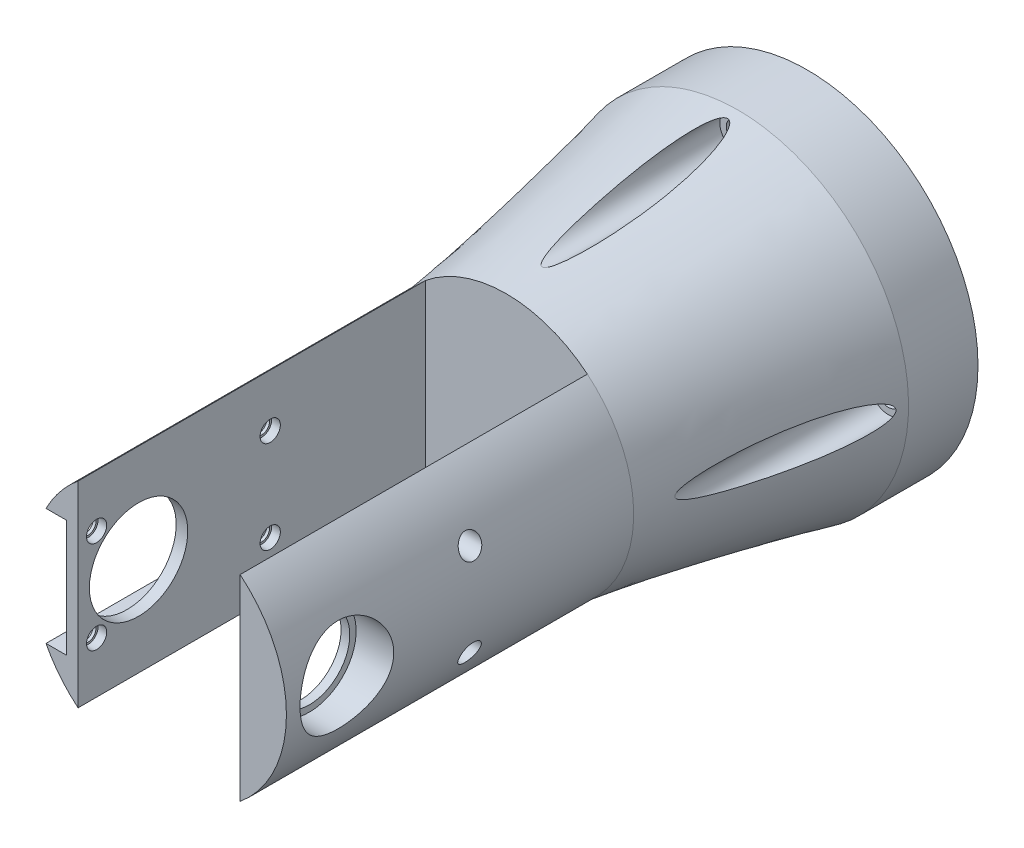
SolidWorks part; units mm, degrees
ref_plane "Front Plane" through (0, 0, 0) normal (0, 0, 1) x (1, 0, 0)
ref_plane "Top Plane" through (0, 0, 0) normal (0, 1, 0) x (1, 0, 0)
ref_plane "Right Plane" through (0, 0, 0) normal (1, 0, 0) x (0, 0, -1)
sketch "Sketch1" plane through (0, 0, 0) normal (0, 0, 1) x (1, 0, 0)
  circle A0 centre (0, 0) radius 29.5
  dimension "D1" = 59
extrude "Boss-Extrude1" add sketch "Sketch1" along normal blind 12
sketch "Sketch2" plane through (0, 0, 12) normal (0, 0, 1) x (1, 0, 0)
  circle A0 centre (0, 0) radius 22
  dimension "D1" = 44
extrude "Boss-Extrude2" add sketch "Sketch2" along normal blind 100 contours A0
sketch "Sketch3" plane through (0, 0, 112) normal (0, 0, 1) x (1, 0, 0)
  line L1 (14, -25) -> (-14, -25)
  line L2 (14, -25) -> (14, 25)
  line L3 (14, 25) -> (-14, 25)
  line L4 (-14, -25) -> (-14, 25)
  line L5 (0, 25) -> (0, -25) construction
  line L6 (14, 0) -> (-14, 0) construction
  point P0 (0, 0)
  dimension "D1" = 28
  dimension "D2" = 50
extrude "Cut-Extrude1" cut sketch "Sketch3" against normal blind 60
sketch "Sketch8" plane through (0, 0, 12) normal (0, 0, 1) x (1, 0, 0)
  circle A0 centre (0, 0) radius 29.5
ref_plane "Plane2" through (0, 0, 52) normal (0, 0, 1) x (1, 0, 0)
sketch "Sketch9" plane through (0, 0, 52) normal (0, 0, 1) x (1, 0, 0)
  circle A0 centre (0, 0) radius 22
loft "Loft2" add profiles "Sketch8", "Sketch9" connector at (6.1194, -28.8583, 12) connector at (-3.7552, -21.6771, 52)
sketch "Sketch11" plane through (0, 0, 0) normal (0, 0, -1) x (-1, 0, 0)
  circle A0 centre (0, -26) radius 2
  circle A1 centre (-26, 0) radius 2
  circle A2 centre (0, 26) radius 2
  circle A3 centre (26, 0) radius 2
  point P12 (0, 0)
  dimension "D1" = 26
  dimension "D2" = 4
  dimension "D3" = 4
extrude "Cut-Extrude3" cut sketch "Sketch11" against normal through all contours A1 | A2 | A3 | A0
sketch "Sketch12" plane through (0, 0, 52) normal (0, 0, 1) x (1, 0, 0)
  circle A0 centre (0, 26) radius 3.1
  circle A1 centre (26, 0) radius 3.1
  circle A2 centre (0, -26) radius 3.1
  circle A3 centre (-26, 0) radius 3.1
  point P12 (0, 0)
  dimension "D1" = 6.2
  dimension "D2" = 4
extrude "Cut-Extrude4" cut sketch "Sketch12" against normal blind 40
sketch "Sketch13" plane through (0, 0, 112) normal (0, 0, 1) x (1, 0, 0)
  line L0 (-14, 0) -> (-14, 10.1)
  line L1 (-14, 16.9706) -> (-14, -16.9706) construction
  line L2 (-14, 16.9706) -> (-14, -16.9706) construction
  line L3 (-14, 0) -> (-14, -10.1)
  line L4 (-14, -10.1) -> (-16, -10.1)
  line L5 (-16, -10.1) -> (-16, 10.1)
  line L6 (-16, 10.1) -> (-14, 10.1)
  line L7 (-16, 10.1) -> (-19.5446, 10.1)
  line L8 (-16, -10.1) -> (-19.5446, -10.1)
  circle A0 centre (0, 0) radius 22 construction
  arc A1 (-14, 16.9706) -> (-14, -16.9706) centre (0, 0) ccw construction
  arc A2 (-19.5446, -10.1) -> (-19.5446, 10.1) centre (0, 0) cw
  dimension "D1" = 10.1
  dimension "D2" = 10.1
  dimension "D3" = 2
extrude "Cut-Extrude7" cut sketch "Sketch13" against normal blind 35 contours A2 L8 L5 L7 region at (-18.651, 0, 112)
sketch "Sketch14" plane through (-16, 0, 0) normal (-1, 0, 0) x (0, 0, 1)
  line L0 (77, -10.1) -> (77, 10.1) construction
  circle A0 centre (101.55, 0) radius 8.5
  dimension "D2" = 17
  dimension "D1" = 24.55
extrude "Cut-Extrude8" cut sketch "Sketch14" against normal blind 10
sketch "Sketch15" plane through (-16, 0, 0) normal (-1, 0, 0) x (0, 0, 1)
  line L0 (78.8, -10.1) -> (78.8, -8.1)
  line L1 (77, -10.1) -> (112, -10.1) construction
  line L2 (78.8, -8.1) -> (77, -8.1)
  line L3 (77, -10.1) -> (77, 10.1) construction
  circle A0 centre (78.8, -8.1) radius 1.4
  circle A1 centre (108.8, -8.1) radius 1.4
  circle A2 centre (108.8, 7.9) radius 1.4
  circle A3 centre (78.8, 7.9) radius 1.4
  dimension "D3" = 2.8
  dimension "D1" = 2
  dimension "D2" = 1.8
  dimension "D4" = 2
  dimension "D5" = 2
extrude "Cut-Extrude9" cut sketch "Sketch15" against normal blind 10 contours A0 | A3 | A1 | A2
sketch "Sketch16" plane through (14, 0, 0) normal (-1, 0, 0) x (0, 0, 1)
  line L1 (112, -16.9706) -> (112, 16.9706) construction
  circle A0 centre (101.55, 0) radius 8.1
  dimension "D1" = 10.45
  dimension "D2" = 16.2
extrude "Cut-Extrude10" cut sketch "Sketch16" against normal blind 10
sketch "Sketch18" plane through (14, 0, 0) normal (-1, 0, 0) x (0, 0, 1)
  circle A0 centre (101.55, 0) radius 7
  circle A1 centre (101.55, 0) radius 8.1
  dimension "D1" = 14
extrude "Boss-Extrude3" add sketch "Sketch18" against normal blind 1.5
sketch "Sketch19" plane through (-14, 0, 0) normal (1, 0, 0) x (0, 0, -1)
  circle A0 centre (-108.8, -8.1) radius 1.75
  circle A1 centre (-78.8, -8.1) radius 1.75
  circle A2 centre (-78.8, 7.9) radius 1.75
  circle A3 centre (-108.8, 7.9) radius 1.75
  dimension "D1" = 3.5
  dimension "D2" = 2
  dimension "D3" = 2
extrude "Cut-Extrude11" cut sketch "Sketch19" against normal blind 1.5
sketch "Sketch20" plane through (14, 0, 0) normal (-1, 0, 0) x (0, 0, 1)
  line L0 (112, -16.9706) -> (112, 16.9706) construction
  line L1 (77, 10) -> (69, 10)
  line L2 (77, 10) -> (77, -10)
  line L3 (77, -10) -> (69, -10)
  line L4 (69, 10) -> (69, -10)
  line L5 (73, -10) -> (73, 10) construction
  line L6 (77, 0) -> (69, 0) construction
  circle A0 centre (101.55, 0) radius 7 construction
  point P0 (73, 0)
  point P8 (112, 0)
  dimension "D1" = 8
  dimension "24,55" = 24.55
  dimension "D2" = 0
  dimension "D3" = 20
sketch "Sketch21" plane through (-14, 0, 0) normal (1, 0, 0) x (0, 0, -1)
  circle A0 centre (-78.8, -8.1) radius 1.9
  circle A1 centre (-78.8, 7.9) radius 1.9
  dimension "D1" = 3.8
  dimension "D2" = 2
extrude "Cut-Extrude13" cut sketch "Sketch21" along normal through all
